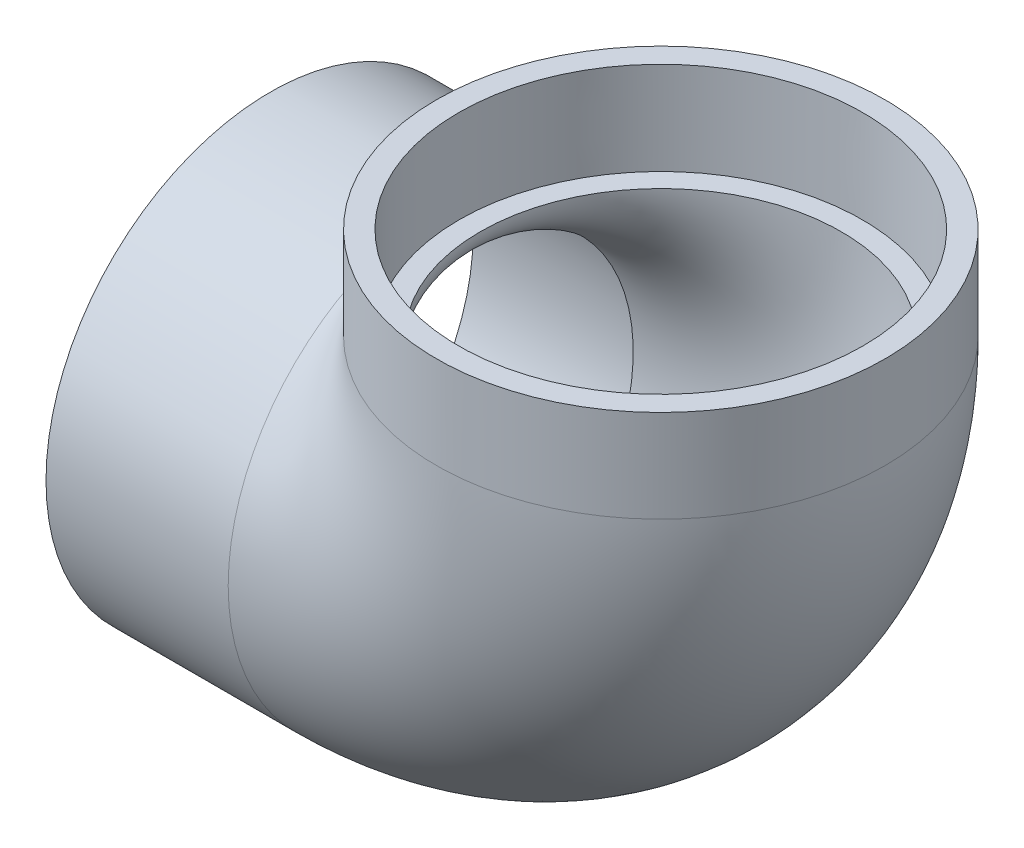
SolidWorks part; units mm, degrees
material "PVC Rigid"
ref_plane "Front Plane" through (0, 0, 0) normal (0, 0, 1) x (1, 0, 0)
ref_plane "Top Plane" through (0, 0, 0) normal (0, 1, 0) x (1, 0, 0)
ref_plane "Right Plane" through (0, 0, 0) normal (1, 0, 0) x (0, 0, -1)
sketch "Sketch0" plane through (0, 0, 0) normal (0, 0, 1) x (1, 0, 0)
  line L0 (-110.49, 0) -> (0, 0) construction
  line L1 (0, 0) -> (0, 110.49) construction
  line L2 (-58.928, 0) -> (0, 0) construction
  line L3 (0, 0) -> (0, 58.928) construction
  line L4 (-110.49, 63.5) -> (-110.49, -63.5) construction
  line L5 (-58.928, 57.0357) -> (-110.49, 57.3786) construction
  line L6 (-58.928, 57.0357) -> (-58.928, -57.0357) construction
  line L7 (-58.928, -57.0357) -> (-110.49, -57.3786) construction
  line L8 (-110.49, 57.3786) -> (-110.49, -57.3786) construction
  line L9 (-63.5, 110.49) -> (63.5, 110.49) construction
  line L10 (-57.3786, 110.49) -> (57.3786, 110.49) construction
  line L11 (57.3786, 110.49) -> (57.0357, 58.928) construction
  line L12 (57.0357, 58.928) -> (-57.0357, 58.928) construction
  line L13 (-57.0357, 58.928) -> (-57.3786, 110.49) construction
  line L14 (-58.928, 51.1302) -> (-58.928, -51.1302) construction
  line L18 (-51.1302, 58.928) -> (51.1302, 58.928) construction
  dimension "H" = 110.49
  dimension "G" = 58.928
  dimension "M" = 127
  dimension "OD A" = 114.7572
  dimension "OD B" = 114.0714
  dimension "ID" = 102.2604
sketch "Sketch1" plane through (0, 0, 0) normal (0, 0, 1) x (1, 0, 0)
  line L0 (-110.49, 0) -> (0, 0) construction
  line L1 (-110.49, 0) -> (0, 0) construction
  line L3 (-110.49, -63.5) -> (-58.928, -63.5)
  line L4 (-110.49, -63.5) -> (-110.49, -57.3786)
  line L5 (-110.49, -57.3786) -> (-58.928, -57.0357)
  line L6 (-58.928, -63.5) -> (-58.928, -57.0357)
revolve "Revolve1" add sketch "Sketch1" angle 360 about L1
sketch "Sketch2" plane through (0, 0, 0) normal (0, 0, 1) x (1, 0, 0)
  line L0 (57.3786, 110.49) -> (57.0357, 58.928)
  line L1 (57.0357, 58.928) -> (63.5, 58.928)
  line L2 (63.5, 58.928) -> (63.5, 110.49)
  line L3 (63.5, 110.49) -> (57.3786, 110.49)
  line L4 (0, 0) -> (0, 110.49) construction
  line L5 (0, 0) -> (0, 110.49) construction
revolve "Revolve2" add sketch "Sketch2" angle 360 about L5
sketch "Sketch3" plane through (-58.928, 0, 0) normal (1, 0, 0) x (0, 0, -1)
  circle A0 centre (0, 0) radius 51.1302
  circle A1 centre (0, 0) radius 63.5
sketch "Sketch4" plane through (0, 0, 0) normal (0, 0, 1) x (1, 0, 0)
  line L0 (-110.49, 0) -> (0, 0) construction
  line L1 (0, 0) -> (0, 110.49) construction
  line L2 (-110.49, 0) -> (-58.928, 0) construction
  line L3 (0, 58.928) -> (0, 110.49) construction
  arc A0 (-58.928, 0) -> (0, 58.928) centre (-58.928, 58.928) ccw
sweep "Sweep1" add profiles "Sketch3" path "Sketch4"
sketch "Sketch5" plane through (0, 110.49, 0) normal (0, 1, 0) x (1, 0, 0)
  circle A0 centre (0, 0) radius 63.5 construction
  circle A1 centre (0, 0) radius 63.5
  circle A2 centre (0, 0) radius 42.7374
extrude "Cut-Extrude1" cut sketch "Sketch5" against normal blind 25.4
